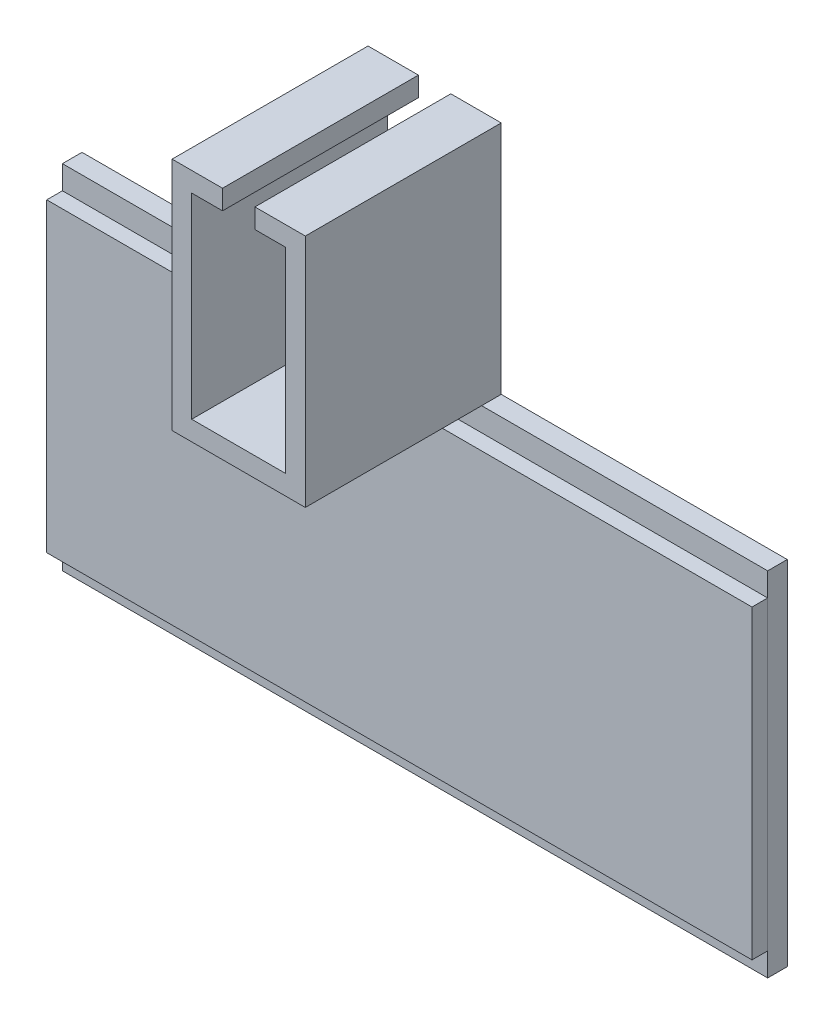
SolidWorks part; units mm, degrees
ref_plane "Ebene vorne" through (0, 0, 0) normal (0, 0, 1) x (1, 0, 0)
ref_plane "Ebene oben" through (0, 0, 0) normal (0, 1, 0) x (1, 0, 0)
ref_plane "Ebene rechts" through (0, 0, 0) normal (1, 0, 0) x (0, 0, -1)
sketch "Skizze1" plane through (0, 0, 0) normal (0, 0, 1) x (1, 0, 0)
  line L0 (-120, 0) -> (120, 0)
  line L1 (120, 0) -> (120, 500)
  line L2 (120, 500) -> (41.3483, 500)
  line L3 (41.3483, 500) -> (41.3483, 550)
  line L4 (41.3483, 550) -> (170, 550)
  line L5 (170, 550) -> (170, -50)
  line L6 (900, -50) -> (900, -950)
  line L7 (900, -950) -> (513.4831, -950)
  line L8 (170, -50) -> (900, -50)
  line L9 (0, -322.4719) -> (0, 738.2022) construction
  line L10 (513.4831, -950) -> (-513.4831, -950)
  line L11 (-170, -50) -> (-900, -50)
  line L12 (-900, -950) -> (-513.4831, -950)
  line L13 (-900, -50) -> (-900, -950)
  line L14 (-170, 550) -> (-170, -50)
  line L15 (-41.3483, 550) -> (-170, 550)
  line L16 (-41.3483, 500) -> (-41.3483, 550)
  line L17 (-120, 500) -> (-41.3483, 500)
  line L18 (-120, 0) -> (-120, 500)
  point P15 (0, -950)
  point P23 (0, 0)
  dimension "D1" = 500
  dimension "D2" = 120
  dimension "D3" = 50
  dimension "D4" = 50
  dimension "D5" = 50
  dimension "D6" = 900
  dimension "D7" = 900
extrude "Aufsatz-Linear austragen1" add sketch "Skizze1" along normal blind 500
sketch "Skizze2" plane through (900, 0, 0) normal (1, 0, 0) x (0, 0, -1)
  line L0 (-500, -50) -> (0, -50) construction
  line L1 (-500, -50) -> (-50, -50)
  line L2 (-500, -50) -> (-500, -950)
  line L3 (-500, -950) -> (-50, -950)
  line L4 (-50, -50) -> (-50, -950)
  line L5 (-500, -950) -> (-500, -50) construction
  line L6 (-500, -950) -> (0, -950) construction
  dimension "D1" = 450
extrude "Schnitt-Linear austragen1" cut sketch "Skizze2" against normal through all
sketch "Skizze3" plane through (900, 0, 0) normal (1, 0, 0) x (0, 0, -1)
  line L0 (-50, -950) -> (-50, -50) construction
  line L1 (-50, -110) -> (-90, -110)
  line L2 (-50, -110) -> (-50, -890)
  line L3 (-50, -890) -> (-90, -890)
  line L4 (-90, -110) -> (-90, -890)
  line L5 (-50, -950) -> (0, -950) construction
  dimension "D1" = 40
  dimension "D2" = 780
  dimension "D3" = 60
extrude "Aufsatz-Linear austragen2" add sketch "Skizze3" against normal blind 1800 separate body
